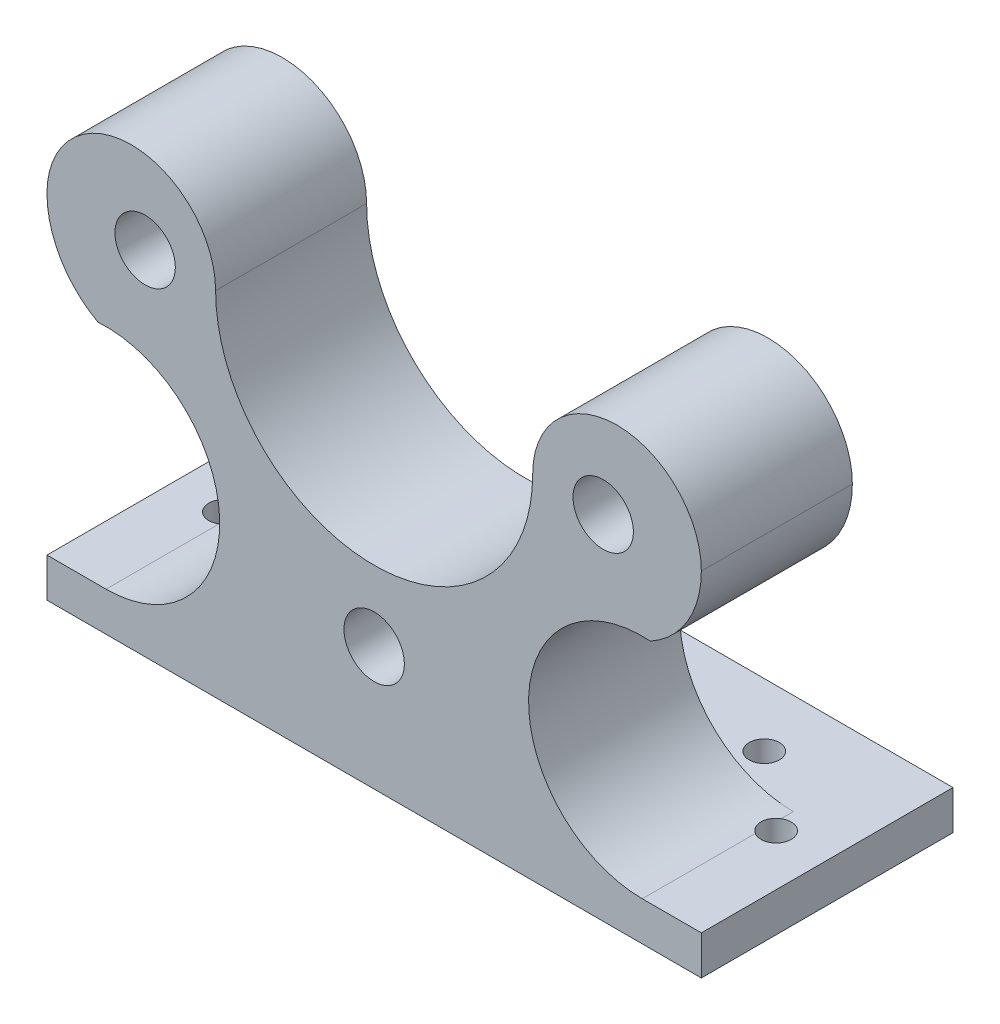
SolidWorks part; units mm, degrees
ref_plane "前视基准面" through (0, 0, 0) normal (0, 0, 1) x (1, 0, 0)
ref_plane "上视基准面" through (0, 0, 0) normal (0, 1, 0) x (1, 0, 0)
ref_plane "右视基准面" through (0, 0, 0) normal (1, 0, 0) x (0, 0, -1)
sketch "草图1" plane through (0, 0, 0) normal (0, 0, 1) x (1, 0, 0)
  line L1 (-48.0628, 80.395) -> (16.9372, 80.395)
  line L2 (-48.0628, 80.395) -> (-48.0628, 10.395)
  line L3 (-48.0628, 10.395) -> (16.9372, 10.395)
  line L4 (16.9372, 80.395) -> (16.9372, 10.395)
extrude "凸台-拉伸1" add sketch "草图1" along normal blind 25
sketch "草图2" plane through (0, 0, 25) normal (0, 0, 1) x (1, 0, 0)
  line L0 (-48.0628, 45.395) -> (16.9372, 45.395) construction
  line L1 (-48.0628, 80.395) -> (-48.0628, 10.395) construction
  line L2 (16.9372, 10.395) -> (16.9372, 80.395) construction
  line L3 (-15.5628, 80.395) -> (-15.5628, 10.395) construction
  line L4 (16.9372, 80.395) -> (-48.0628, 80.395) construction
  line L5 (-48.0628, 10.395) -> (16.9372, 10.395) construction
  circle A0 centre (-15.5628, 45.395) radius 15.75
  dimension "D1" = 31.5
extrude "切除-拉伸1" cut sketch "草图2" against normal through all
sketch "草图4" plane through (0, 0, 0) normal (0, 0, -1) x (-1, 0, 0)
  circle A1 centre (15.5628, 45.395) radius 15.75 construction
  circle A2 centre (15.5628, 45.395) radius 15.75 construction
  circle A3 centre (15.5628, 45.395) radius 22.75 construction
  circle A4 centre (-7.1872, 45.395) radius 3
  point P16 (-5.31, 42.2979)
  dimension "D1" = 45.5
extrude "切除-拉伸2" cut sketch "草图4" against normal blind 40
pattern_circular "阵列(圆周)1" count 4 every 90 about axis through (-15.5628, 45.395, 0) along (0, 0, 1) of "切除-拉伸2"
sketch "草图6" plane through (0, 0, 25) normal (0, 0, 1) x (1, 0, 0)
  line L0 (-38.3128, 45.395) -> (7.1872, 45.395) construction
  line L1 (-48.0628, 80.395) -> (-48.0628, 10.395) construction
  line L2 (16.9372, 10.395) -> (16.9372, 80.395) construction
  line L3 (-31.3128, 45.395) -> (0.1872, 45.395)
  line L4 (16.9372, 80.395) -> (-48.0628, 80.395) construction
  line L5 (16.9372, 80.395) -> (-48.0628, 80.395)
  line L6 (-48.0628, 80.395) -> (-48.0628, 45.395)
  line L7 (16.9372, 80.395) -> (16.9372, 45.395)
  line L8 (7.1872, 45.395) -> (25.4036, 45.395) construction
  circle A0 centre (-15.5628, 45.395) radius 15.75 construction
  circle A1 centre (-15.5628, 45.395) radius 15.75 construction
  arc A2 (-31.3128, 45.395) -> (-48.0628, 45.395) centre (-39.6878, 45.395) ccw
  arc A3 (0.1872, 45.395) -> (16.9372, 45.395) centre (8.5622, 45.395) cw
extrude "切除-拉伸3" cut sketch "草图6" against normal through all
ref_plane "基准面4" through (-15.5628, 0, 0) normal (-1, 0, 0) x (0, 0, 1)
sketch "草图7" plane through (0, 0, 25) normal (0, 0, 1) x (1, 0, 0)
  line L1 (-48.0628, 45.395) -> (-48.0628, 14.2784)
  line L2 (-48.0628, 45.395) -> (-48.0628, 10.395) construction
  line L3 (-48.0628, 45.395) -> (-48.0628, 14.2784) construction
  line L6 (-42.1971, 14.2784) -> (-48.0628, 14.2784)
  arc A1 (-48.0628, 45.395) -> (-42.9934, 36.8419) centre (-38.3128, 45.395) ccw
  arc A3 (-42.9934, 36.8419) -> (-42.1971, 14.2784) centre (-42.1971, 25.5742) cw
extrude "切除-拉伸5" cut sketch "草图7" against normal through all and the other way blind 20
mirror "镜向1" about plane through (-15.5628, 0, 0) normal (-1, 0, 0) of "切除-拉伸5"
sketch "草图8" plane through (0, 10.395, 0) normal (0, -1, 0) x (1, 0, 0)
  line L0 (-48.0628, 12.5) -> (16.9372, 12.5) construction
  line L3 (-15.5628, 25) -> (-15.5628, 0) construction
  line L4 (-48.0628, 25) -> (16.9372, 25) construction
  line L5 (-48.0628, 0) -> (16.9372, 0) construction
  line L7 (-42.9934, 0) -> (-30.9013, 0) construction
  line L8 (-42.9934, 0) -> (-42.9934, 12.5) construction
  line L9 (-42.9934, 0) -> (-30.9013, 0) construction
  line L10 (-42.9934, 6.25) -> (-15.5628, 6.25) construction
  circle A0 centre (-15.5628, 12.5) radius 12.5 construction
  circle A1 centre (-28.0628, 12.5) radius 1.25
  circle A2 centre (-15.5628, 12.5) radius 20 construction
  circle A4 centre (-42.9934, 12.5) radius 1.5
  circle A5 centre (-15.5628, 6.25) radius 20 construction
  circle A6 centre (-35.5628, 6.25) radius 1.5
extrude "切除-拉伸6" cut sketch "草图8" against normal blind 10
mirror "镜向2" about plane through (-15.5628, 0, 0) normal (-1, 0, 0) of "切除-拉伸6"
sketch "草图9" plane through (0, 0, 0) normal (0, 0, -1) x (-1, 0, 0)
  line L0 (-16.9372, 14.2784) -> (-11.0715, 14.2784) construction
  line L1 (56.464, 76.5116) -> (-25.3384, 76.5116)
  line L2 (56.464, 76.5116) -> (56.464, 14.2784)
  line L3 (56.464, 14.2784) -> (-25.3384, 14.2784)
  line L4 (-25.3384, 76.5116) -> (-25.3384, 14.2784)
  line L5 (56.464, 76.5116) -> (-25.3384, 14.2784) construction
  line L6 (56.464, 14.2784) -> (-25.3384, 76.5116) construction
  line L7 (-16.9372, 14.2784) -> (-11.0715, 14.2784) construction
  point P0 (15.5628, 45.395)
extrude "切除-拉伸7" cut sketch "草图9" against normal blind 10
